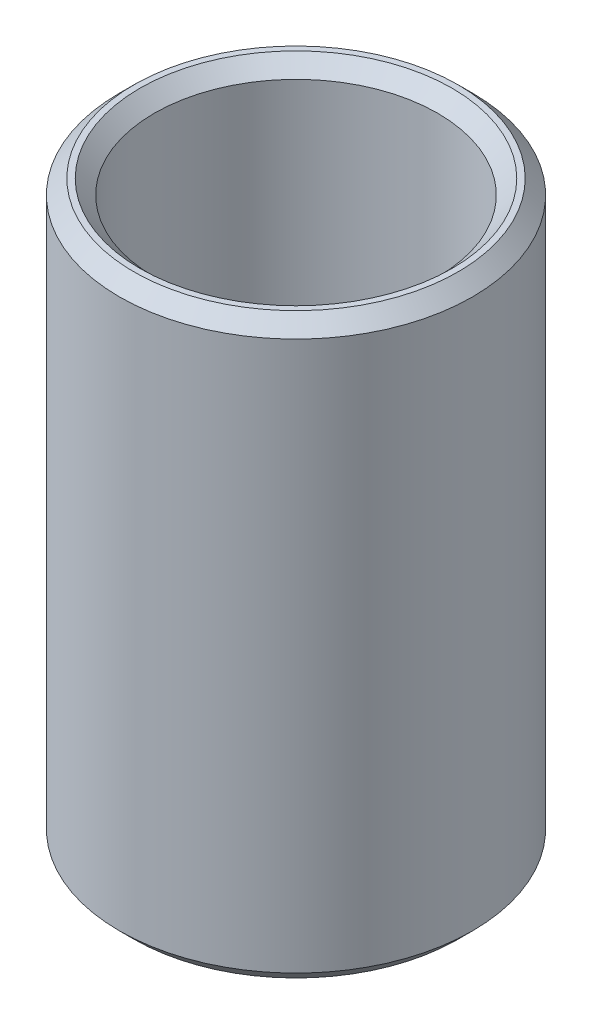
SolidWorks part; units mm, degrees
ref_plane "Front Plane" through (0, 0, 0) normal (0, 0, 1) x (1, 0, 0)
ref_plane "Top Plane" through (0, 0, 0) normal (0, 1, 0) x (1, 0, 0)
ref_plane "Right Plane" through (0, 0, 0) normal (1, 0, 0) x (0, 0, -1)
sketch "Sketch1" plane through (0, 0, 0) normal (0, 1, 0) x (1, 0, 0)
  circle A0 centre (0, 0) radius 45
  dimension "SLEEVE_OD" = 90
extrude "Boss-Extrude1" add sketch "Sketch1" along normal blind 147.3343
sketch "Sketch2" plane through (0, 0, 0) normal (0, 1, 0) x (1, 0, 0)
  circle A0 centre (0, 0) radius 36.1185
  dimension "BORE_D" = 72.2369
extrude "Cut-Extrude1" cut sketch "Sketch2" along normal through all
chamfer "Chamfer1" distance 3.6802 angle 45 4 edges at (0, 147.3343, 36.1185) (0, 0, 36.1185) (0, 0, 45) (0, 147.3343, 45)
